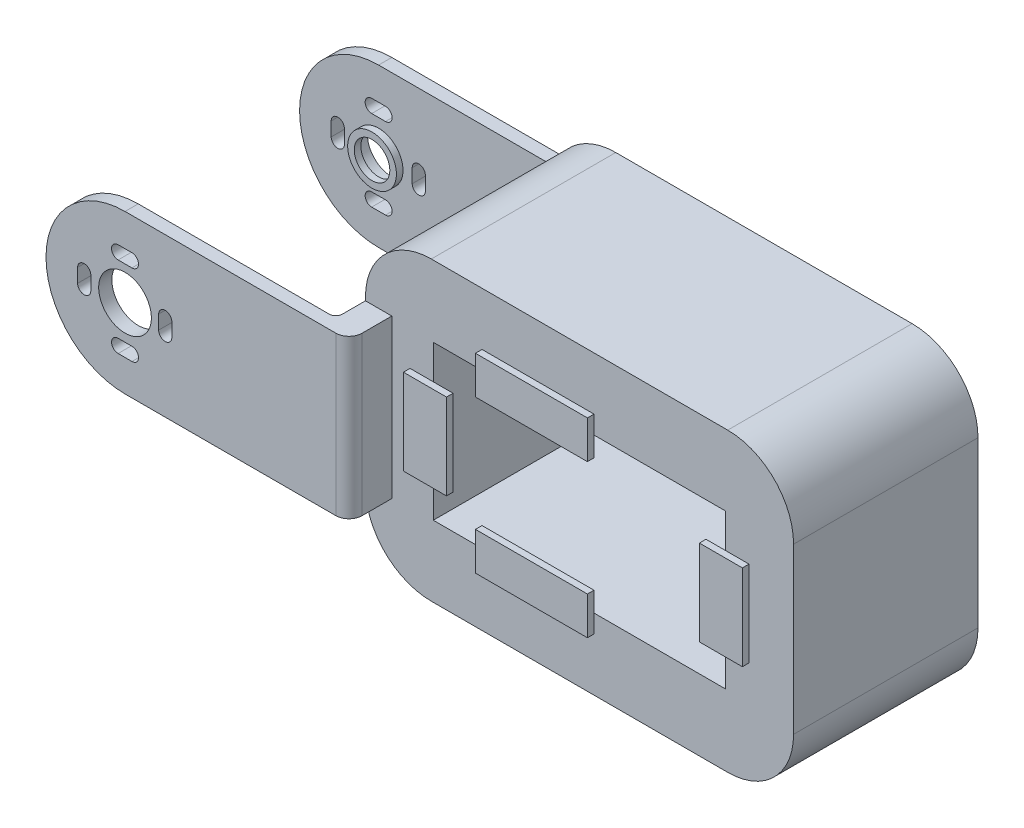
SolidWorks part; units mm, degrees
ref_plane "前基準面" through (0, 0, 0) normal (0, 0, 1) x (1, 0, 0)
ref_plane "上基準面" through (0, 0, 0) normal (0, 1, 0) x (1, 0, 0)
ref_plane "右基準面" through (0, 0, 0) normal (1, 0, 0) x (0, 0, -1)
sketch "草圖1" plane through (0, 0, 0) normal (0, 0, 1) x (1, 0, 0)
  line L0 (-9.02, 0) -> (7.9922, 0) construction
  line L2 (-59.9347, 22.5) -> (5.0653, 22.5)
  line L3 (-59.9347, 22.5) -> (-59.9347, -22.5)
  line L4 (-59.9347, -22.5) -> (5.0653, -22.5)
  line L5 (5.0653, 22.5) -> (5.0653, -22.5)
  dimension "D1" = 45
  dimension "D2" = 22.5
  dimension "D3" = 65
extrude "填料-伸長1" add sketch "草圖1" along normal blind 28
sketch "草圖2" plane through (0, 0, 0) normal (0, 0, 1) x (1, 0, 0)
  line L0 (-59.9347, 0) -> (5.361, 0) construction
  line L1 (-59.9347, 22.5) -> (-59.9347, -22.5) construction
  line L2 (-27.4347, 22.5) -> (-27.4347, -22.5) construction
  line L3 (5.0653, 22.5) -> (-59.9347, 22.5) construction
  line L4 (-59.9347, -22.5) -> (5.0653, -22.5) construction
  line L6 (-49.6347, 11.7) -> (-5.2347, 11.7)
  line L7 (-49.6347, 11.7) -> (-49.6347, -11.7)
  line L8 (-49.6347, -11.7) -> (-5.2347, -11.7)
  line L9 (-5.2347, 11.7) -> (-5.2347, -11.7)
  dimension "D1" = 44.4
  dimension "D2" = 23.4
  dimension "D3" = 10.3
  dimension "D4" = 10.8
extrude "除料-伸長1" cut sketch "草圖2" along normal blind 39
ref_plane "平面1" through (0, 0, 28) normal (0, 0, 1) x (1, 0, 0)
sketch "草圖3" plane through (0, 0, 28) normal (0, 0, 1) x (1, 0, 0)
  line L0 (-59.9347, 22.5) -> (-59.9347, -22.5) construction
  line L2 (-59.9347, 12) -> (-55.9347, 12)
  line L3 (-59.9347, 12) -> (-59.9347, -12)
  line L4 (-59.9347, -12) -> (-55.9347, -12)
  line L5 (-55.9347, 12) -> (-55.9347, -12)
  line L8 (-5.2347, -11.7) -> (-49.6347, -11.7) construction
  dimension "D1" = 4
  dimension "D2" = 24
  dimension "D3" = 0.3
extrude "填料-伸長2" add sketch "草圖3" along normal blind 6
ref_plane "平面2" through (-59.9347, 0, 0) normal (-1, 0, 0) x (0, 0, 1)
sketch "草圖4" plane through (-59.9347, 0, 0) normal (-1, 0, 0) x (0, 0, 1)
  line L0 (34, 12) -> (28, 12) construction
  line L2 (32, 12) -> (34, 12)
  line L3 (32, 12) -> (32, -12)
  line L4 (32, -12) -> (34, -12)
  line L5 (34, 12) -> (34, -12)
  dimension "D1" = 2
ref_plane "平面3" through (0, 0, 33) normal (0, 0, 1) x (1, 0, 0)
sketch "草圖6" plane through (0, 0, 28) normal (0, 0, 1) x (1, 0, 0)
  line L0 (-15.2347, 0.3) -> (5.0653, -22.5)
  line L1 (-5.2347, 11.7) -> (-5.2347, -11.7) construction
  line L2 (-5.2347, -11.7) -> (-49.6347, -11.7) construction
  line L3 (-15.2347, 0.3) -> (-15.2347, -22.5)
  line L4 (-59.9347, -22.5) -> (5.0653, -22.5) construction
  line L5 (-15.2347, -22.5) -> (5.0653, -22.5)
  dimension "D1" = 10
  dimension "D2" = 12
sketch "草圖7" plane through (0, 0, 33) normal (0, 0, 1) x (1, 0, 0)
  line L1 (-59.9347, 12) -> (-59.9347, -12) construction
  line L3 (-59.9347, 0) -> (-109.9347, 0) construction
  line L5 (-96.1347, 1.05) -> (-96.1347, -1.05) construction
  line L6 (-95.1347, 1.05) -> (-95.1347, -1.05)
  line L7 (-97.1347, 1.05) -> (-97.1347, -1.05)
  line L8 (-90.9847, -6.2) -> (-88.8847, -6.2) construction
  line L9 (-90.9847, -5.2) -> (-88.8847, -5.2)
  line L10 (-90.9847, -7.2) -> (-88.8847, -7.2)
  line L11 (-89.9347, 4) -> (-89.9347, -7.9506) construction
  line L12 (-90.9847, 6.1) -> (-88.8847, 6.1) construction
  line L13 (-90.9847, 5.1) -> (-88.8847, 5.1)
  line L14 (-90.9847, 7.1) -> (-88.8847, 7.1)
  line L15 (-83.8347, 1.05) -> (-83.8347, -1.05) construction
  line L16 (-84.8347, 1.05) -> (-84.8347, -1.05)
  line L17 (-82.8347, 1.05) -> (-82.8347, -1.05)
  line L19 (-59.9347, 12) -> (-59.9347, -12)
  line L20 (-59.9347, -12) -> (-89.9347, -12)
  line L21 (-59.9347, 12) -> (-89.9347, 12)
  circle A1 centre (-89.9347, 0) radius 4
  arc A3 (-95.1347, 1.05) -> (-97.1347, 1.05) centre (-96.1347, 1.05) ccw
  arc A4 (-97.1347, -1.05) -> (-95.1347, -1.05) centre (-96.1347, -1.05) ccw
  arc A5 (-90.9847, -5.2) -> (-90.9847, -7.2) centre (-90.9847, -6.2) ccw
  arc A6 (-88.8847, -7.2) -> (-88.8847, -5.2) centre (-88.8847, -6.2) ccw
  arc A7 (-90.9847, 5.1) -> (-90.9847, 7.1) centre (-90.9847, 6.1) cw
  arc A8 (-88.8847, 7.1) -> (-88.8847, 5.1) centre (-88.8847, 6.1) cw
  arc A9 (-84.8347, 1.05) -> (-82.8347, 1.05) centre (-83.8347, 1.05) cw
  arc A10 (-82.8347, -1.05) -> (-84.8347, -1.05) centre (-83.8347, -1.05) cw
  arc A11 (-89.9347, 12) -> (-89.9347, -12) centre (-89.9347, 0) ccw
  point P15 (-96.1347, 0)
  point P20 (-89.9347, -6.2)
  point P31 (-89.9347, 6.1)
  point P38 (-83.8347, 0)
  dimension "D2" = 8
  dimension "D3" = 50
  dimension "D4" = 6.2
  dimension "D6" = 0
  dimension "D5" = 2.1
  dimension "D7" = 2
  dimension "D8" = 2
  dimension "D9" = 0
  dimension "D10" = 2.1
  dimension "D11" = 6.2
extrude "填料-伸長3" add sketch "草圖7" along normal blind 1.5 and the other way blind 0.5
ref_plane "平面4" through (0, 0, 0) normal (0, 0, -1) x (-1, 0, 0)
sketch "草圖8" plane through (0, 0, 0) normal (0, 0, -1) x (-1, 0, 0)
  line L0 (59.9347, 12) -> (59.9347, -12) construction
  line L1 (55.9347, 12) -> (59.9347, 12)
  line L2 (55.9347, 12) -> (55.9347, -12)
  line L3 (55.9347, -12) -> (59.9347, -12)
  line L4 (59.9347, 12) -> (59.9347, -12)
  dimension "D1" = 24
  dimension "D2" = 4
extrude "填料-伸長4" add sketch "草圖8" along normal blind 6 contours L3 L4 L1 L2
fillet "圓角1" radius 10 1 edges at (-59.9347, -22.5, 14) type face fillet first side face at (-59.9347, 0, 13.75) second side face at (-27.4347, -22.5, 14)
fillet "圓角2" radius 10 1 edges at (-59.9347, 22.5, 14) type face fillet first side face at (-27.4347, 22.5, 14) second side face at (-59.9347, 1.6667, 13.75)
fillet "圓角3" radius 10 1 edges at (5.0653, 22.5, 14) type face fillet first side face at (-22.4347, 22.5, 14) second side face at (5.0653, 0, 14)
fillet "圓角4" radius 10 1 edges at (5.0653, -22.5, 14) type face fillet first side face at (-22.4347, -22.5, 14) second side face at (5.0653, -5, 14)
pattern_linear "直線複製排列2" count 2 spacing 38.5 along (0, 0, -1) of "填料-伸長3"
fillet "圓角5" radius 2 1 edges at (-55.9347, 0, -6) type face fillet first side face at (-75.9347, 0, -6) second side face at (-55.9347, 0, -3)
ref_plane "平面5" through (0, 0, -4) normal (0, 0, 1) x (1, 0, 0)
sketch "草圖9" plane through (0, 0, -4) normal (0, 0, 1) x (1, 0, 0)
  circle A0 centre (-89.9347, 0) radius 3.7
  circle A1 centre (-89.9347, 0) radius 2.7
  dimension "D1" = 7.4
  dimension "D2" = 5.4
extrude "填料-伸長5" add sketch "草圖9" along normal blind 1 separate body
ref_plane "平面6" through (0, 0, 29) normal (0, 0, 1) x (1, 0, 0)
sketch "草圖10" plane through (0, 0, 29) normal (0, 0, 1) x (1, 0, 0)
  line L6 (-49.6347, 0) -> (-4.2092, 0) construction
  line L7 (-49.6347, -11.7) -> (-49.6347, 11.7) construction
  line L8 (-27.4347, -11.7) -> (-27.4347, 19.297) construction
  line L9 (-5.2347, -11.7) -> (-49.6347, -11.7) construction
  line L11 (-49.6347, 6.5) -> (-53.1651, 6.5)
  line L14 (-53.1651, 6.5) -> (-53.1651, -6.5)
  line L17 (-49.6347, 6.5) -> (-46.6347, 6.5)
  line L18 (-46.6347, 6.5) -> (-46.6347, -6.5)
  line L20 (-42.2347, -11.7) -> (-42.2347, -8.7)
  line L25 (-42.2347, -11.7) -> (-42.2347, -14.4546)
  line L27 (-8.2347, 6.5) -> (-8.2347, -6.5)
  line L28 (-8.2347, -6.5) -> (-5.2347, -6.5)
  line L29 (-5.2347, -6.5) -> (-1.7043, -6.5)
  line L30 (-1.7043, 6.5) -> (-1.7043, -6.5)
  line L32 (-25.2347, 8.7) -> (-25.2347, 14.4546)
  line L33 (-25.2347, -14.4546) -> (-25.2347, -8.7)
  line L34 (-25.2347, -14.4546) -> (-42.2347, -14.4546)
  line L35 (-25.2347, -8.7) -> (-42.2347, -8.7)
  line L36 (-25.2347, 8.7) -> (-42.2347, 8.7)
  line L37 (-25.2347, 14.4546) -> (-42.2347, 14.4546)
  line L38 (-42.2347, 8.7) -> (-42.2347, 14.4546)
  line L39 (-46.6347, -6.5) -> (-53.1651, -6.5)
  line L40 (-1.7043, 6.5) -> (-8.2347, 6.5)
  dimension "D3" = 13
  dimension "D4" = 6.5
extrude "填料-伸長6" add sketch "草圖10" against normal blind 1 separate body
ref_plane "平面7" through (0, 0, -4) normal (0, 0, -1) x (-1, 0, 0)
sketch "草圖12" plane through (0, 0, -4) normal (0, 0, -1) x (-1, 0, 0)
  circle A0 centre (89.9347, 0) radius 4
  circle A1 centre (89.9347, 0) radius 3.7
extrude "填料-伸長8" add sketch "草圖12" along normal blind 2
ref_plane "平面9" through (0, 0, 34) normal (0, 0, 1) x (1, 0, 0)
sketch "草圖15" plane through (0, 0, 34) normal (0, 0, 1) x (1, 0, 0)
  line L0 (-59.9347, 12) -> (-59.9347, -12) construction
  line L1 (-59.9347, 12) -> (-55.9347, 12)
  line L2 (-59.9347, 12) -> (-59.9347, -12)
  line L3 (-59.9347, -12) -> (-55.9347, -12)
  line L4 (-55.9347, 12) -> (-55.9347, -12)
  line L5 (-55.9347, 12) -> (-59.9347, 12) construction
  dimension "D1" = 24
  dimension "D2" = 4
extrude "填料-伸長10" add sketch "草圖15" along normal blind 0.5
fillet "圓角16" radius 2 1 edges at (-55.9347, 0, 34.5) type face fillet first side face at (-75.9347, 0, 34.5) second side face at (-55.9347, 0, 31.25)
fillet "圓角17" radius 1 1 edges at (-59.9347, 0, 32.5) type face fillet first side face at (-83.8347, 0, 32.5) second side face at (-59.9347, 0, 14.0833)
fillet "圓角18" radius 1 1 edges at (-59.9347, 0, -4) type face fillet first side face at (-59.9347, 0, 13.9167) second side face at (-77.9347, 0, -4)
